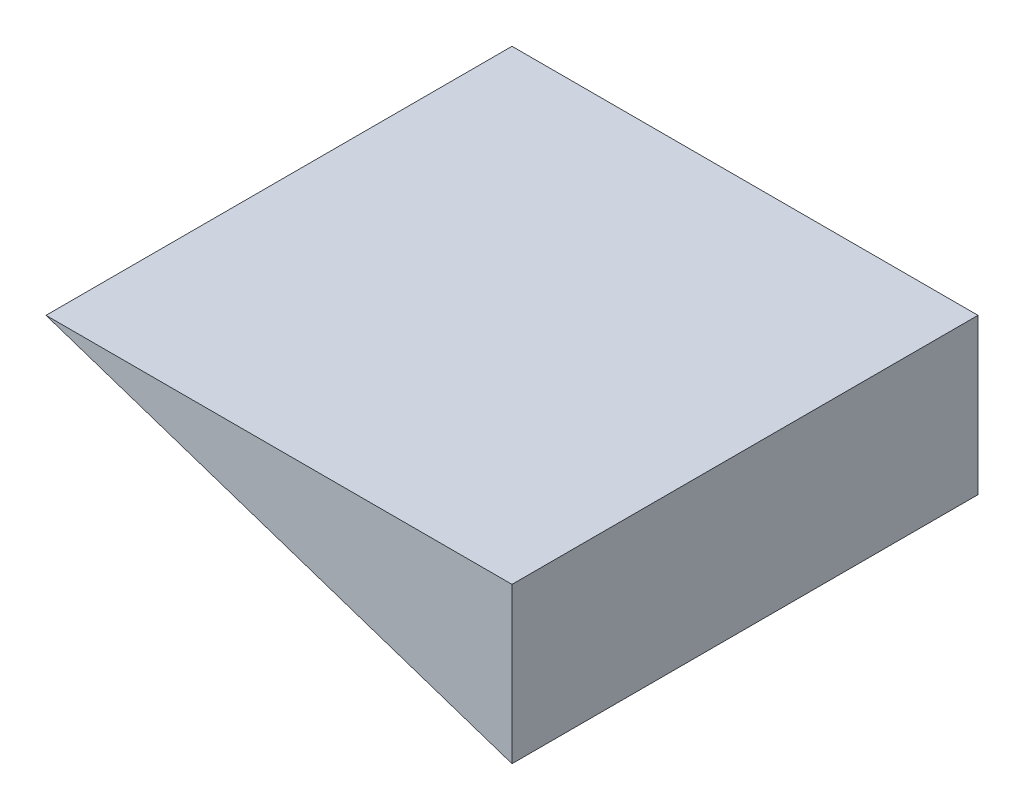
SolidWorks part; units mm, degrees
ref_plane "Front Plane" through (0, 0, 0) normal (0, 0, 1) x (1, 0, 0)
ref_plane "Top Plane" through (0, 0, 0) normal (0, 1, 0) x (1, 0, 0)
ref_plane "Right Plane" through (0, 0, 0) normal (1, 0, 0) x (0, 0, -1)
sketch "Sketch1" plane through (0, 0, 0) normal (0, 0, 1) x (1, 0, 0)
  line L1 (-150, 50) -> (150, 50)
  line L2 (-150, 50) -> (-150, -50)
  line L3 (-150, -50) -> (150, -50)
  line L4 (150, 50) -> (150, -50)
  line L5 (-150, 50) -> (150, -50) construction
  line L6 (-150, -50) -> (150, 50) construction
  point P0 (0, 0)
  dimension "D1" = 100
  dimension "D2" = 300
extrude "Boss-Extrude1" add sketch "Sketch1" against normal blind 300
sketch "Sketch2" plane through (0, 0, 0) normal (0, 0, 1) x (1, 0, 0)
  line L0 (-150, 50) -> (-150, -50)
  line L1 (-150, -50) -> (150, -50)
  line L2 (150, -50) -> (-150, 50)
sketch "Sketch3" plane through (-150, 0, 0) normal (-1, 0, 0) x (0, 0, 1)
  line L0 (-300, -50) -> (0, -50) construction
  line L1 (-6, -50) -> (-294, -50)
  line L2 (-6, -50) -> (-6, 44)
  line L3 (-6, 44) -> (-294, 44)
  line L4 (-294, -50) -> (-294, 44)
  line L5 (-300, 50) -> (0, 50) construction
  line L6 (-300, 50) -> (-300, -50) construction
  line L7 (0, -50) -> (0, 50) construction
  dimension "D1" = 6
  dimension "D2" = 6
  dimension "D3" = 6
extrude "Cut-Extrude2" cut sketch "Sketch3" against normal blind 294
extrude "Cut-Extrude3" cut sketch "Sketch2" against normal blind 316
scale "Scale1" scale about origin uniform scaling yes scale factor 0.001
